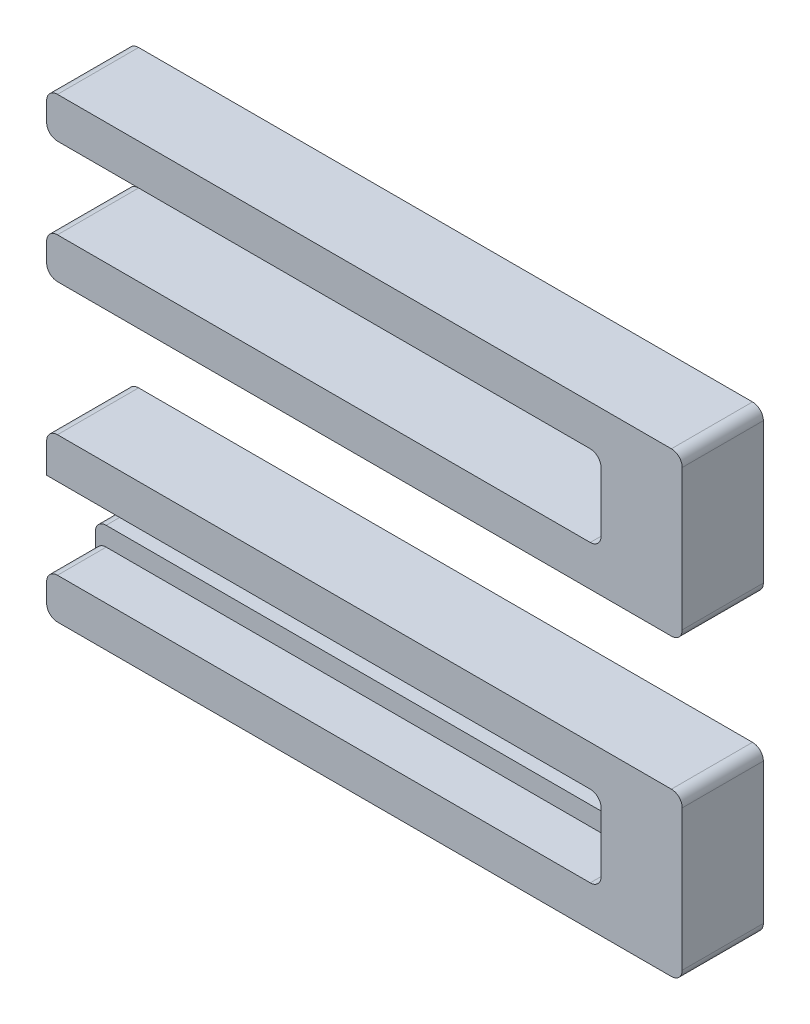
SolidWorks part; units mm, degrees
ref_plane "Front Plane" through (0, 0, 0) normal (0, 0, 1) x (1, 0, 0)
ref_plane "Top Plane" through (0, 0, 0) normal (0, 1, 0) x (1, 0, 0)
ref_plane "Right Plane" through (0, 0, 0) normal (1, 0, 0) x (0, 0, -1)
sketch "Sketch2" plane through (0, 0, 0) normal (0, 0, 1) x (1, 0, 0)
  line L0 (-2.7742, -2.4497) -> (31.3823, -2.4497) construction
  line L1 (0, 0) -> (23.5, 0)
  line L2 (0, 0) -> (0, 6)
  line L3 (0, 6) -> (23.5, 6)
  line L4 (23.5, 0) -> (23.5, 6)
  line L5 (0, 4.5) -> (20.5, 4.5)
  line L6 (0, 4.5) -> (0, 1.5)
  line L7 (0, 1.5) -> (20.5, 1.5)
  line L8 (20.5, 4.5) -> (20.5, 1.5)
  line L9 (0, 4.5) -> (20.5, 4.5)
  line L10 (0, 4.5) -> (0, 3.8)
  line L11 (0, 3.8) -> (20.5, 3.8)
  line L12 (20.5, 4.5) -> (20.5, 3.8)
  line L13 (20.5, -9.3995) -> (20.5, -8.6995)
  line L14 (0, -8.6995) -> (20.5, -8.6995)
  line L15 (0, -9.3995) -> (0, -8.6995)
  line L16 (0, -9.3995) -> (20.5, -9.3995)
  line L17 (20.5, -9.3995) -> (20.5, -6.3995)
  line L18 (0, -6.3995) -> (20.5, -6.3995)
  line L19 (0, -9.3995) -> (0, -6.3995)
  line L20 (0, -9.3995) -> (20.5, -9.3995)
  line L21 (23.5, -4.8995) -> (23.5, -10.8995)
  line L22 (0, -10.8995) -> (23.5, -10.8995)
  line L23 (0, -4.8995) -> (0, -10.8995)
  line L24 (0, -4.8995) -> (23.5, -4.8995)
  dimension "D1" = 6
  dimension "D2" = 3
  dimension "D3" = 1.5
  dimension "D4" = 3
  dimension "D5" = 20.5
  dimension "D6" = 2.3
extrude "Boss-Extrude1" add sketch "Sketch2" along normal blind 3 contours L5 L8 L7 L2 L1 L4 L3 | L24 L23 L18 L17 L13 L16 L22 L21 region at (0.2425, 0.75, 0) region at (20.7425, -9.0495, 0)
extrude "Boss-Extrude3" add sketch "Sketch2<4>" along normal blind 1.2 contours L15 L16 L13 L14 | L6 L11 L8 L5 region at (10.25, 4.15, 0) region at (10.25, -9.0495, 0)
sketch "Sketch2<4>" plane through (0, 0, 0) normal (0, 0, 1) x (1, 0, 0) same geometry as "Sketch2"
fillet "Fillet2" radius 0.4 10 edges at (0, 4.5, 2.1) (20.5, 1.5, 1.5) (20.5, 3.8, 0.6) (20.5, 4.5, 2.1) (23.5, 6, 1.5) (23.5, 0, 1.5) (0, 0, 1.5) (0, 1.5, 1.5) (0, 3.8, 0.6) (0, 6, 1.5)
fillet "Fillet3" radius 0.4 9 edges at (23.5, -10.8995, 1.5) (23.5, -4.8995, 1.5) (20.5, -6.3995, 1.5) (20.5, -9.3995, 2.1) (20.5, -8.6995, 0.6) (0, -10.8995, 1.5) (0, -9.3995, 2.1) (0, -8.6995, 0.6) (0, -4.8995, 1.5)
